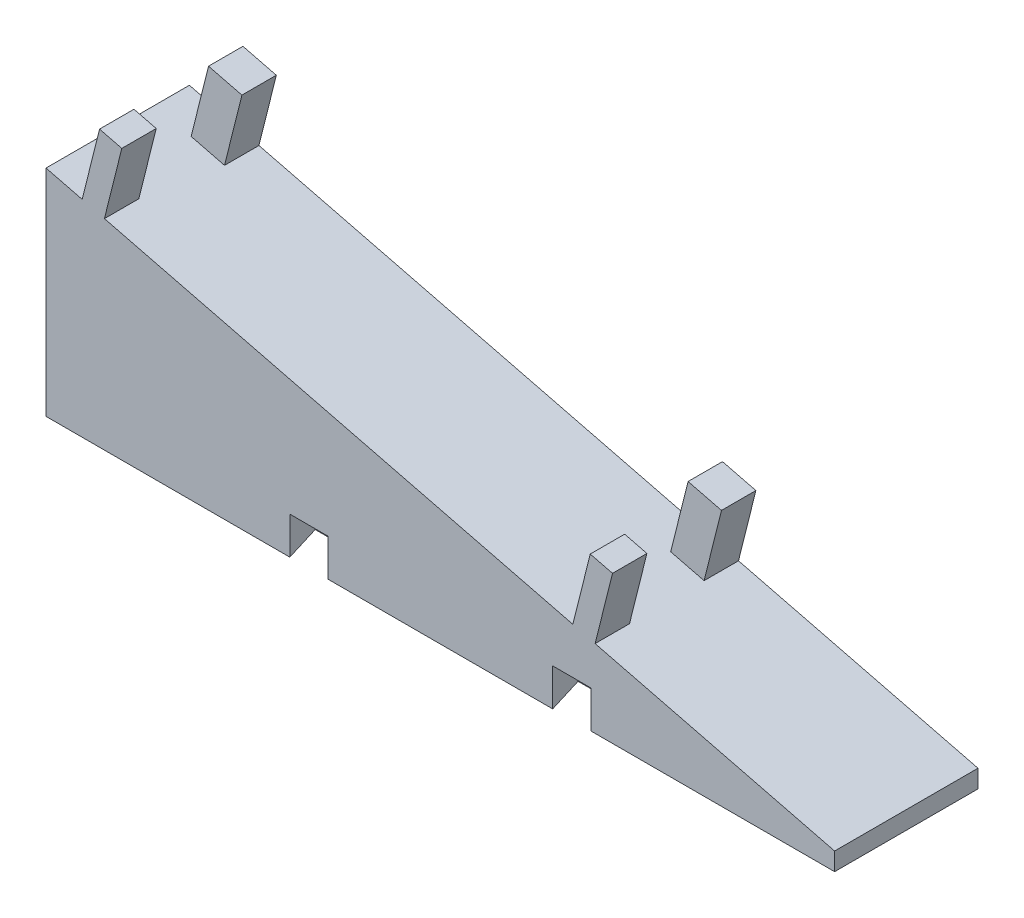
SolidWorks part; units mm, degrees
ref_plane "Front Plane" through (0, 0, 0) normal (0, 0, 1) x (1, 0, 0)
ref_plane "Top Plane" through (0, 0, 0) normal (0, 1, 0) x (1, 0, 0)
ref_plane "Right Plane" through (0, 0, 0) normal (1, 0, 0) x (0, 0, -1)
sketch "Sketch1" plane through (0, 0, 0) normal (0, 0, 1) x (1, 0, 0)
  line L0 (-55, 21.875) -> (55, -5.625)
  line L1 (0, 8.125) -> (0, -8.125) construction
  line L2 (-55, 21.875) -> (-55, -8.125)
  line L3 (-55, -8.125) -> (55, -8.125)
  line L4 (55, -5.625) -> (55, -8.125)
  point P3 (65, -8.125)
  point P7 (0, 0)
  dimension "D1" = 110
  dimension "D2" = 10
  dimension "D3" = 30
extrude "Boss-Extrude1" add sketch "Sketch1" along normal blind 10 and the other way blind 10
sketch "Sketch2" plane through (1.9118, 7.6471, 0) normal (0.2425, 0.9701, 0) x (0.9701, -0.2425, 0)
  line L0 (-80.1847, 0) -> (-56.0217, 0) construction
  line L1 (-53.4633, 10) -> (-48.6633, 10)
  line L2 (-53.4633, 10) -> (-53.4633, 5.2)
  line L3 (-53.4633, 5.2) -> (-48.6633, 5.2)
  line L4 (-48.6633, 10) -> (-48.6633, 5.2)
  line L5 (-58.6633, 10) -> (-58.6633, -10) construction
  line L6 (54.7221, -10) -> (-58.6633, -10) construction
  line L7 (54.7221, 10) -> (-58.6633, 10) construction
  line L8 (-53.4633, -10) -> (-50.2633, -10)
  line L9 (-53.4633, -10) -> (-53.4633, -5.2)
  line L10 (-53.4633, -5.2) -> (-50.2633, -5.2)
  line L11 (-50.2633, -5.2) -> (-50.2633, -10)
  line L12 (17.0867, -5.2) -> (17.0867, -10)
  line L13 (20.2867, 10) -> (15.4867, 10)
  line L14 (20.2867, 10) -> (20.2867, 5.2)
  line L15 (20.2867, 5.2) -> (15.4867, 5.2)
  line L16 (15.4867, 10) -> (15.4867, 5.2)
  line L17 (20.2867, -5.2) -> (17.0867, -5.2)
  line L18 (20.2867, -5.2) -> (20.2867, -10)
  line L19 (20.2867, -10) -> (17.0867, -10)
  dimension "D1" = 5.2
  dimension "D2" = 5.2
  dimension "D3" = 3.2
  dimension "D4" = 73.75
  dimension "D5" = 4.8
extrude "Boss-Extrude2" add sketch "Sketch2" along normal blind 10
sketch "Sketch3" plane through (0, -8.125, 0) normal (0, -1, 0) x (1, 0, 0)
  line L0 (-55, -10) -> (55, -10) construction
  line L1 (-55, -4.9) -> (-18.3333, -4.9) construction
  line L2 (-55, -10) -> (-55, 10) construction
  line L3 (-18.3333, -4.9) -> (18.3333, -4.9) construction
  line L4 (18.3333, -4.9) -> (55, -4.9) construction
  line L5 (55, -10) -> (55, 10) construction
  line L6 (-55, 0) -> (55, 0) construction
  line L7 (18.3333, 4.9) -> (55, 4.9) construction
  line L8 (-18.3333, 4.9) -> (18.3333, 4.9) construction
  line L9 (-55, 4.9) -> (-18.3333, 4.9) construction
  line B0 (15.8833, -10) -> (20.7833, -10) construction
  line B1 (15.6921, -10.0585) -> (14.1129, -4.9)
  line B2 (14.1129, -4.9) -> (22.5537, -4.9)
  line B3 (22.5537, -4.9) -> (20.9746, -10.0585)
  line B4 (20.9746, -10.0585) -> (15.6921, -10.0585)
  line B5 (-20.9746, -10.0585) -> (-22.5537, -4.9)
  line B6 (-22.5537, -4.9) -> (-14.1129, -4.9)
  line B7 (-14.1129, -4.9) -> (-15.6921, -10.0585)
  line B8 (-15.6921, -10.0585) -> (-20.9746, -10.0585)
  line B9 (-20.9746, 10.0585) -> (-22.5537, 4.9)
  line B10 (-22.5537, 4.9) -> (-14.1129, 4.9)
  line B11 (-14.1129, 4.9) -> (-15.6921, 10.0585)
  line B12 (-15.6921, 10.0585) -> (-20.9746, 10.0585)
  line B13 (15.6921, 10.0585) -> (14.1129, 4.9)
  line B14 (14.1129, 4.9) -> (22.5537, 4.9)
  line B15 (22.5537, 4.9) -> (20.9746, 10.0585)
  line B16 (20.9746, 10.0585) -> (15.6921, 10.0585)
sketch_block_instance "Block1-2"
sketch_block "Block1"
sketch_block_instance "Block1-3"
sketch_block_instance "Block1-4"
sketch_block_instance "Block1-5"
extrude "Cut-Extrude1" cut sketch "Sketch3" against normal blind 5.2
